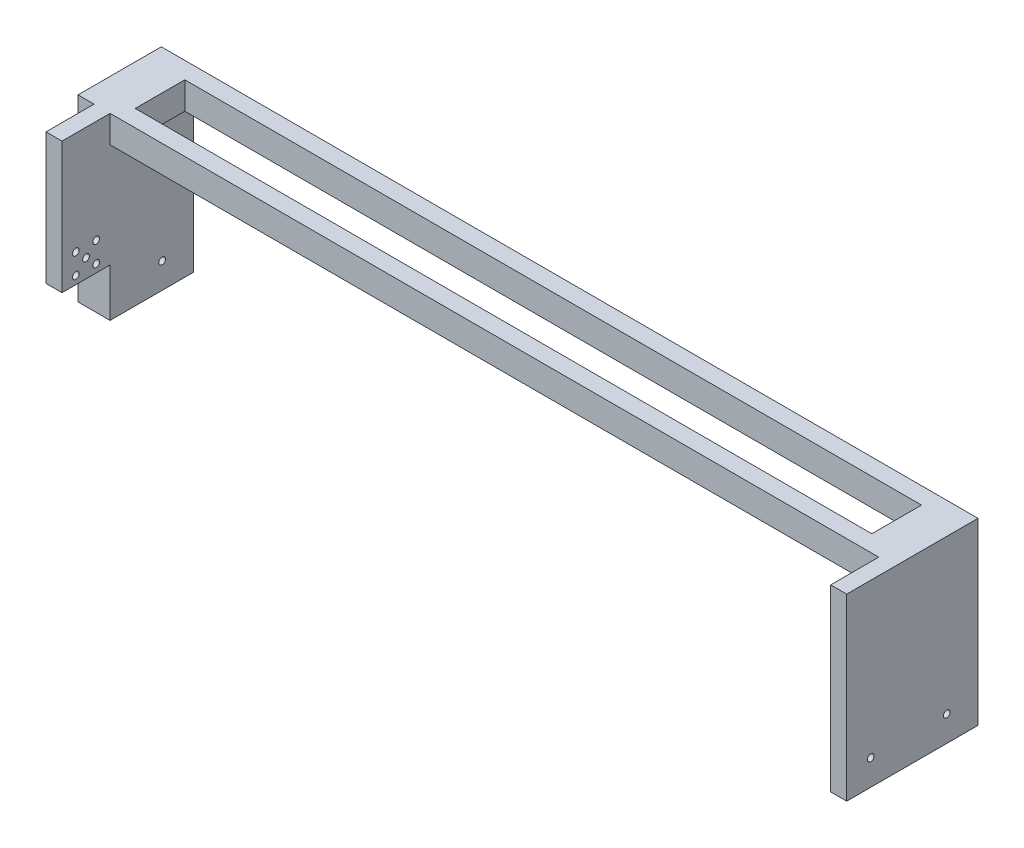
SolidWorks part; units mm, degrees
ref_plane "Front Plane" through (0, 0, 0) normal (0, 0, 1) x (1, 0, 0)
ref_plane "Top Plane" through (0, 0, 0) normal (0, 1, 0) x (1, 0, 0)
ref_plane "Right Plane" through (0, 0, 0) normal (1, 0, 0) x (0, 0, -1)
sketch "Sketch1" plane through (0, 0, 0) normal (0, 1, 0) x (1, 0, 0)
  line L0 (10, -82) -> (10, -52)
  line L1 (10, -52) -> (0, -52)
  line L2 (0, -52) -> (0, 0)
  line L4 (0, 0) -> (510, 0)
  line L5 (510, 0) -> (510, -82)
  line L8 (510, -82) -> (500, -82)
  line L9 (20, -82) -> (20, -52)
  line L10 (20, -52) -> (500, -52)
  line L11 (500, -52) -> (500, -82)
  line L12 (20, -82) -> (10, -82)
  dimension "D1" = 480
  dimension "D2" = 510
  dimension "D3" = 10
  dimension "D4" = 10
  dimension "D5" = 52
  dimension "D6" = 30
  dimension "D7" = 30
extrude "Boss-Extrude1" add sketch "Sketch1" along normal blind 82 and the other way blind 0.001 contours L9 L10 L11 L8 L5 L4 L2 L1 L0 L12
sketch "Sketch2" plane through (0, 0, 0) normal (0, 0, 1) x (1, 0, 0)
  line L0 (20, -0.001) -> (20, 64.999)
  line L1 (20, 82) -> (20, -0.001) construction
  line L2 (20, 64.999) -> (500, 64.999)
  line L3 (500, 82) -> (500, -0.001) construction
  line L4 (500, 64.999) -> (500, -0.001)
  line L5 (500, -0.001) -> (20, -0.001)
  dimension "D1" = 65
extrude "Cut-Extrude2" cut sketch "Sketch2" along normal blind 82
sketch "Sketch3" plane through (0, 0, 0) normal (0, 1, 0) x (1, 0, 0)
  line L0 (20, -82) -> (20, -52) construction
  line L1 (0, 0) -> (20, 0)
  line L2 (0, 0) -> (0, -52)
  line L3 (0, -52) -> (20, -52)
  line L4 (20, 0) -> (20, -52)
  line L5 (0, 0) -> (510, 0) construction
  line L6 (500, 0) -> (510, 0)
  line L7 (500, 0) -> (500, -82)
  line L8 (500, -82) -> (510, -82)
  line L9 (510, 0) -> (510, -82)
  line L10 (500, -52) -> (500, -82) construction
  line L11 (10, -52) -> (0, -52) construction
extrude "Boss-Extrude3" add sketch "Sketch3" against normal blind 30
sketch "Sketch4" plane through (510, 0, 0) normal (1, 0, 0) x (0, 0, -1)
  line L0 (-82, -30) -> (0, -30) construction
  line L2 (-82, -30) -> (-82, 82) construction
  circle A0 centre (-67, -14.051) radius 2.1
  circle A1 centre (-19.5, -14.05) radius 2.1
  dimension "D1" = 4.2
  dimension "D2" = 4.2
  dimension "D3" = 15.949
  dimension "D4" = 15
  dimension "D5" = 15.95
  dimension "D6" = 47.5
extrude "Cut-Extrude3" cut sketch "Sketch4" against normal blind 618
sketch "Sketch5" plane through (0, 82, 0) normal (0, 1, 0) x (1, 0, 0)
  line L0 (25.2, 0) -> (25.2, -52) construction
  line L1 (0, 0) -> (510, 0) construction
  line L3 (20, -52) -> (500, -52) construction
  line L4 (485.2, 0) -> (485.2, -52) construction
  line L5 (485.2, -103.8096) -> (485.2, 946.1904) construction
  line L6 (25.2, -10.5) -> (485.2, -10.5)
  line L7 (25.2, -10.5) -> (25.2, -41.5)
  line L8 (25.2, -41.5) -> (485.2, -41.5)
  line L9 (485.2, -41.5) -> (485.2, -10.5)
  line L10 (25.2, -103.8096) -> (25.2, 946.1904) construction
  dimension "D1" = 10.5
  dimension "D2" = 31
extrude "Cut-Extrude4" cut sketch "Sketch5" against normal blind 42
sketch "Sketch6" plane through (20, 0, 0) normal (1, 0, 0) x (0, 0, -1)
  line L0 (-82, -0.001) -> (-52, -0.001) construction
  line L3 (-67, -0.001) -> (-67, 29.5711) construction
  circle A0 centre (-67, 11.349) radius 2.1
  circle A1 centre (-60.65, 17.699) radius 2.1
  circle A2 centre (-73.35, 17.699) radius 2.1
  circle A3 centre (-73.35, 4.999) radius 2.1
  circle A4 centre (-60.65, 4.999) radius 2.1
  dimension "D5" = 4.2
  dimension "D6" = 12.7
  dimension "D1" = 12.7
  dimension "D2" = 6.35
  dimension "D3" = 12.7
  dimension "D4" = 6.35
  dimension "D7" = 6.35
  dimension "D8" = 6.35
  dimension "D9" = 6.35
  dimension "D10" = 5
  dimension "D11" = 29.5721
extrude "Cut-Extrude5" cut sketch "Sketch6" against normal blind 10
